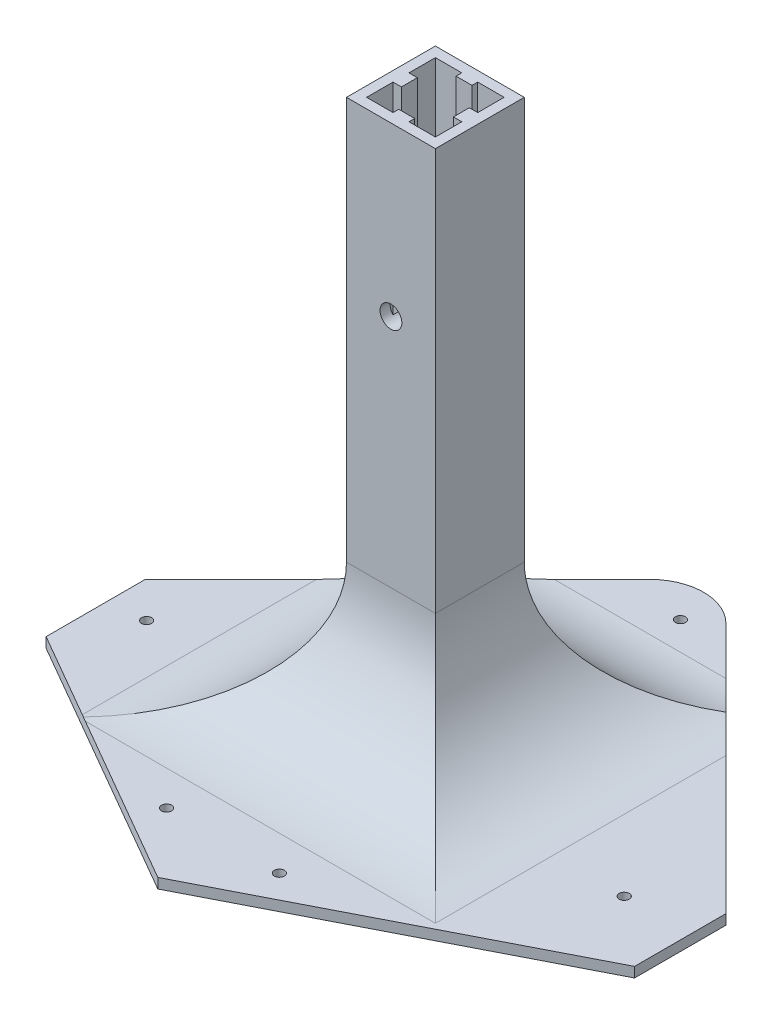
SolidWorks part; units mm, degrees
ref_plane "Alzado" through (0, 0, 0) normal (0, 0, 1) x (1, 0, 0)
ref_plane "Planta" through (0, 0, 0) normal (0, 1, 0) x (1, 0, 0)
ref_plane "Vista lateral" through (0, 0, 0) normal (1, 0, 0) x (0, 0, -1)
sketch "Croquis1" plane through (0, 0, 0) normal (0, 1, 0) x (1, 0, 0)
  line L0 (56.5976, -1117.0407) -> (-18.6736, -1041.7696) construction
  line L1 (56.5976, -1117.0407) -> (56.5976, -1145.3018) construction
  line L2 (56.5976, -1145.3018) -> (-38.4725, -1193.9169) construction
  line L3 (-38.4725, -1193.9169) -> (-118.2589, -1147.8522) construction
  line L4 (-118.2589, -1147.8522) -> (-118.2589, -1117.3133) construction
  line L5 (-42.7152, -1041.7696) -> (-118.2589, -1117.3133) construction
  line L6 (56.5976, -1117.0407) -> (-18.6736, -1041.7696) construction
  line L7 (56.5976, -1117.0407) -> (56.5976, -1145.3018) construction
  line L8 (56.5976, -1145.3018) -> (-38.4725, -1193.9169) construction
  line L9 (-38.4725, -1193.9169) -> (-118.2589, -1147.8522) construction
  line L10 (-118.2589, -1147.8522) -> (-118.2589, -1117.3133) construction
  line L11 (-42.7152, -1041.7696) -> (-118.2589, -1117.3133) construction
  line L24 (-42.0081, -1042.4767) -> (-117.2589, -1117.7275)
  line L25 (-117.2589, -1117.7275) -> (-117.2589, -1147.2748)
  line L26 (-117.2589, -1147.2748) -> (-38.4436, -1192.7789)
  line L27 (-38.4436, -1192.7789) -> (55.5976, -1144.69)
  line L28 (55.5976, -1144.69) -> (55.5976, -1117.4549)
  line L29 (55.5976, -1117.4549) -> (-19.3807, -1042.4767)
  line L30 (-42.0081, -1042.4767) -> (-117.2589, -1117.7275)
  line L31 (-117.2589, -1117.7275) -> (-117.2589, -1147.2748)
  line L32 (-117.2589, -1147.2748) -> (-38.4436, -1192.7789)
  line L33 (-38.4436, -1192.7789) -> (55.5976, -1144.69)
  line L34 (55.5976, -1144.69) -> (55.5976, -1117.4549)
  line L35 (55.5976, -1117.4549) -> (-19.3807, -1042.4767)
  arc A0 (-18.6736, -1041.7696) -> (-42.7152, -1041.7696) centre (-30.6944, -1053.7904) ccw construction
  arc A1 (-18.6736, -1041.7696) -> (-42.7152, -1041.7696) centre (-30.6944, -1053.7904) ccw construction
  arc A4 (-19.3807, -1042.4767) -> (-42.0081, -1042.4767) centre (-30.6944, -1053.7904) ccw
  arc A5 (-19.3807, -1042.4767) -> (-42.0081, -1042.4767) centre (-30.6944, -1053.7904) ccw
  dimension "D1" = 1
extrude "Saliente-Extruir1" add sketch "Croquis1" along normal blind 3
sketch "Croquis2" plane through (0, 3, 0) normal (0, 1, 0) x (1, 0, 0)
  line L0 (-51.7225, -1096.75) -> (-51.7225, -1123.25)
  line L1 (-48.7225, -1099.75) -> (-28.2225, -1099.75)
  line L2 (-48.7225, -1099.75) -> (-48.7225, -1120.25)
  line L3 (-48.7225, -1120.25) -> (-28.2225, -1120.25)
  line L4 (-28.2225, -1099.75) -> (-28.2225, -1120.25)
  line L5 (-48.7225, -1099.75) -> (-28.2225, -1120.25) construction
  line L6 (-48.7225, -1120.25) -> (-28.2225, -1099.75) construction
  line L7 (-51.7225, -1123.25) -> (-25.2225, -1123.25)
  line L8 (-25.2225, -1096.75) -> (-25.2225, -1123.25)
  line L9 (-51.7225, -1096.75) -> (-25.2225, -1096.75)
  line L10 (-38.4725, -1096.75) -> (-38.4725, -1123.25) construction
  circle A0 centre (-38.4725, -1110) radius 5 construction
  circle A1 centre (-38.4725, -1110) radius 5 construction
  dimension "D1" = 20.5
  dimension "D2" = 20.5
  dimension "D3" = 3
extrude "Saliente-Extruir2" add sketch "Croquis2" along normal blind 160
fillet "Redondeo1" radius 40 4 edges at (-38.4725, 3, 1096.75) (-51.7225, 3, 1110) (-25.2225, 3, 1110) (-38.4725, 3, 1123.25)
sketch "Croquis3" plane through (0, 0, 0) normal (0, 1, 0) x (1, 0, 0)
  line L3 (-28.2225, -1120.25) -> (-28.2225, -1099.75)
  line L5 (-28.2225, -1120.25) -> (-28.2225, -1099.75)
  line L7 (-28.2225, -1099.75) -> (-48.7225, -1099.75)
  line L14 (-28.2225, -1099.75) -> (-48.7225, -1099.75)
  line L15 (-48.7225, -1099.75) -> (-48.7225, -1120.25)
  line L16 (-48.7225, -1099.75) -> (-48.7225, -1120.25)
  line L17 (-48.7225, -1120.25) -> (-28.2225, -1120.25)
  line L18 (-48.7225, -1120.25) -> (-28.2225, -1120.25)
  dimension "D1" = 0
extrude "Saliente-Extruir3" add sketch "Croquis3" along normal blind 12
sketch "Croquis5" plane through (0, 12, 0) normal (0, 1, 0) x (1, 0, 0)
  line L0 (-28.2225, -1110) -> (-48.7225, -1110) construction
  line L1 (-28.2225, -1120.25) -> (-28.2225, -1099.75) construction
  line L2 (-48.7225, -1099.75) -> (-48.7225, -1120.25) construction
  line L3 (-38.4725, -1099.75) -> (-38.4725, -1120.25) construction
  line L4 (-28.2225, -1099.75) -> (-48.7225, -1099.75) construction
  line L5 (-48.7225, -1120.25) -> (-28.2225, -1120.25) construction
  circle A0 centre (-38.4725, -1110) radius 4.5
  point P14 (0, 0)
  dimension "D1" = 9
extrude "Cortar-Extruir1" cut sketch "Croquis5" against normal through all both and the other way through all
sketch "Croquis6" plane through (0, 12, 0) normal (0, 1, 0) x (1, 0, 0)
  line L1 (-38.4725, -1102.148) -> (-45.2725, -1106.074)
  line L2 (-45.2725, -1106.074) -> (-45.2725, -1113.926)
  line L3 (-45.2725, -1113.926) -> (-38.4725, -1117.852)
  line L4 (-38.4725, -1117.852) -> (-31.6725, -1113.926)
  line L5 (-31.6725, -1113.926) -> (-31.6725, -1106.074)
  line L6 (-31.6725, -1106.074) -> (-38.4725, -1102.148)
  circle A0 centre (-38.4725, -1110) radius 6.8 construction
  dimension "D1" = 13.6
extrude "Cortar-Extruir2" cut sketch "Croquis6" against normal blind 8
sketch "Croquis7" plane through (0, 12, 0) normal (0, 1, 0) x (1, 0, 0)
  line L0 (-38.4725, -1096.75) -> (-38.4725, -1123.25) construction
  line L1 (-25.2225, -1096.75) -> (-51.7225, -1096.75) construction
  line L2 (-51.7225, -1123.25) -> (-25.2225, -1123.25) construction
  line L3 (-51.7225, -1110) -> (-25.2225, -1110) construction
  line L4 (-51.7225, -1096.75) -> (-51.7225, -1123.25) construction
  line L5 (-25.2225, -1123.25) -> (-25.2225, -1096.75) construction
  line L6 (-40.8475, -1099.75) -> (-40.8475, -1101.45)
  line L7 (-28.2225, -1099.75) -> (-48.7225, -1099.75) construction
  line L8 (-40.8475, -1101.45) -> (-36.0975, -1101.45)
  line L9 (-48.7225, -1107.625) -> (-46.2225, -1107.625)
  line L10 (-48.7225, -1099.75) -> (-48.7225, -1120.25) construction
  line L11 (-46.2225, -1107.625) -> (-46.2225, -1112.375)
  line L12 (-36.0975, -1099.75) -> (-36.0975, -1101.45)
  line L13 (-48.7225, -1112.375) -> (-46.2225, -1112.375)
  line L14 (-36.0975, -1120.25) -> (-36.0975, -1118.55)
  line L15 (-40.8475, -1118.55) -> (-36.0975, -1118.55)
  line L16 (-40.8475, -1120.25) -> (-40.8475, -1118.55)
  line L17 (-28.2225, -1112.375) -> (-30.7225, -1112.375)
  line L18 (-30.7225, -1107.625) -> (-30.7225, -1112.375)
  line L19 (-28.2225, -1107.625) -> (-30.7225, -1107.625)
  line L20 (-40.8475, -1120.25) -> (-36.0975, -1120.25)
  line L21 (-48.7225, -1107.625) -> (-48.7225, -1112.375)
  line L22 (-40.8475, -1099.75) -> (-36.0975, -1099.75)
  line L23 (-28.2225, -1107.625) -> (-28.2225, -1112.375)
  point P23 (-38.4725, -1101.45)
  point P25 (-46.2225, -1110)
  dimension "D1" = 1.7
  dimension "D2" = 2.5
  dimension "D3" = 4.75
  dimension "D4" = 4.75
extrude "Saliente-Extruir4" add sketch "Croquis7" along normal up to surface (151 mm away) up to face at (-38.4725, 163, 1110)
sketch "Croquis8" plane through (0, 0, 1123.25) normal (0, 0, 1) x (1, 0, 0)
  line L0 (-38.4725, 163) -> (-38.4725, 115.0276) construction
  line L1 (-51.7225, 163) -> (-25.2225, 163) construction
  circle A0 centre (-38.4725, 113) radius 3.25
  dimension "D1" = 6.5
  dimension "D2" = 50
extrude "Cortar-Extruir4" cut sketch "Croquis8" against normal through all both and the other way through all
sketch "Croquis9" plane through (0, 3, 0) normal (0, 1, 0) x (1, 0, 0)
  circle A5 centre (-27.0907, -1048.333) radius 1.5
  circle A6 centre (-106.4285, -1128.1413) radius 1.5
  circle A7 centre (-55.0376, -1173.573) radius 1.5
  circle A8 centre (-21.4127, -1173.573) radius 1.5
  circle A9 centre (35.9662, -1128.1413) radius 1.5
extrude "Cortar-Extruir5" cut sketch "Croquis9" against normal through all
